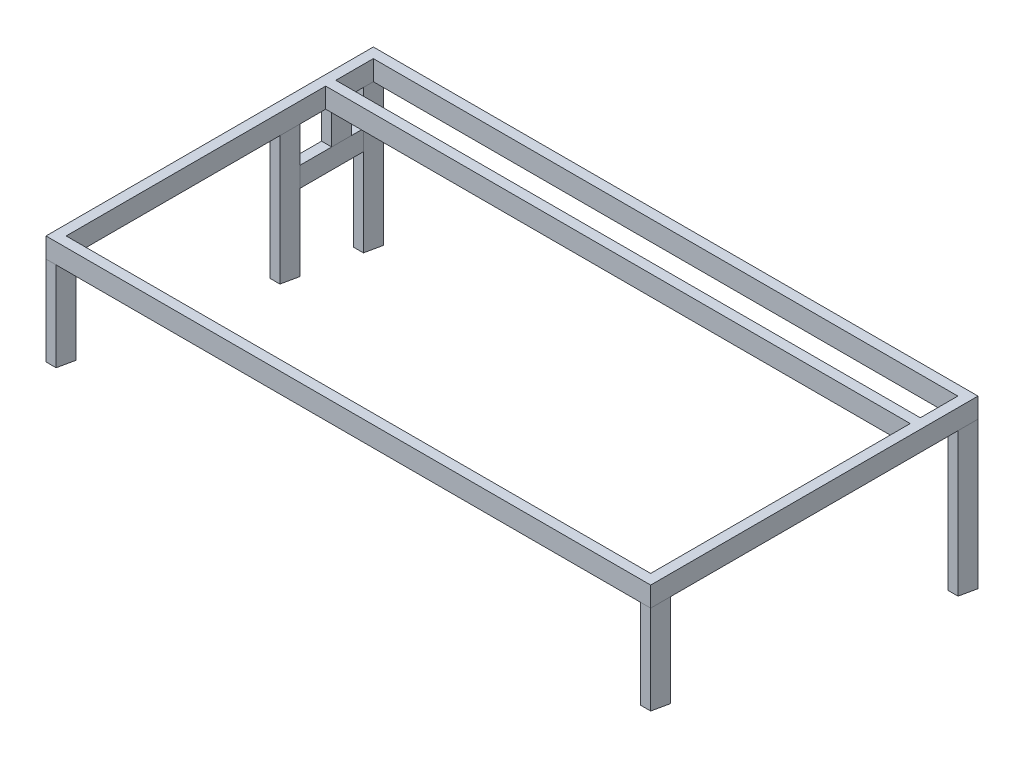
SolidWorks part; units mm, degrees
ref_plane "Front Plane" through (0, 0, 0) normal (0, 0, 1) x (1, 0, 0)
ref_plane "Top Plane" through (0, 0, 0) normal (0, 1, 0) x (1, 0, 0)
ref_plane "Right Plane" through (0, 0, 0) normal (1, 0, 0) x (0, 0, -1)
sketch "Sketch22" plane through (0, 0, 0) normal (0, 1, 0) x (1, 0, 0)
  line L0 (-736.6, 387.1) -> (736.6, 387.1)
  line L1 (-762, 412.5) -> (762, 412.5)
  line L2 (-762, 412.5) -> (-762, -412.5)
  line L3 (-762, -412.5) -> (762, -412.5)
  line L4 (762, 412.5) -> (762, -412.5)
  line L5 (-762, 412.5) -> (762, -412.5) construction
  line L6 (-762, -412.5) -> (762, 412.5) construction
  line L7 (736.6, 387.1) -> (736.6, -387.1)
  line L8 (-736.6, -387.1) -> (736.6, -387.1)
  line L9 (-736.6, 387.1) -> (-736.6, -387.1)
  point P0 (0, 0)
  dimension "D1" = 1524
  dimension "D2" = 825
  dimension "D3" = 25.4
extrude "Boss-Extrude3" add sketch "Sketch22" against normal blind 50.4
ref_plane "Plane1" through (0, -275, 0) normal (0, 1, 0) x (1, 0, 0)
ref_plane "Plane2" through (0, 0, 412.5) normal (0, 0, 1) x (1, 0, 0)
ref_axis "Axis1" through (-838.2, -275, 412.5) along (1, 0, 0)
ref_plane "LAUNCH PLANE" through (0, -337.2494, 59.4662) normal (0, 0.9848, -0.1736) x (1, 0, 0)
sketch "Sketch23" plane through (0, -50.4, 0) normal (0, -1, 0) x (1, 0, 0)
  line L0 (-736.6, -387.1) -> (-736.6, 387.1) construction
  line L1 (-762, 412.5) -> (-736.6, 412.5)
  line L2 (-762, 412.5) -> (-762, 362.1)
  line L3 (-762, 362.1) -> (-736.6, 362.1)
  line L4 (-736.6, 412.5) -> (-736.6, 362.1)
  line L5 (0, 0) -> (0, 277.5925) construction
  line L6 (736.6, 412.5) -> (736.6, 362.1)
  line L7 (762, 362.1) -> (736.6, 362.1)
  line L8 (762, 412.5) -> (762, 362.1)
  line L9 (762, 412.5) -> (736.6, 412.5)
  dimension "D1" = 50.4
extrude "Boss-Extrude4" add sketch "Sketch23" along normal up to surface (224.6 mm away) separate body up to plane "LAUNCH PLANE"
sketch "Sketch24" plane through (0, -50.4, 0) normal (0, -1, 0) x (1, 0, 0)
  line L0 (-736.6, -387.1) -> (-736.6, 387.1) construction
  line L1 (-762, -412.5) -> (-736.6, -412.5)
  line L2 (-762, -412.5) -> (-762, -362.1)
  line L3 (-762, -362.1) -> (-736.6, -362.1)
  line L4 (-736.6, -412.5) -> (-736.6, -362.1)
  line L5 (0, 0) -> (0, -131.3731) construction
  line L6 (736.6, -412.5) -> (736.6, -362.1)
  line L7 (762, -362.1) -> (736.6, -362.1)
  line L8 (762, -412.5) -> (762, -362.1)
  line L9 (762, -412.5) -> (736.6, -412.5)
  line L10 (-762, -412.5) -> (-762, 412.5) construction
  line L16 (-736.6, -202.1) -> (-762, -202.1)
  line L17 (-736.6, -202.1) -> (-736.6, -151.7)
  line L18 (-736.6, -151.7) -> (-762, -151.7)
  line L19 (-762, -202.1) -> (-762, -151.7)
  dimension "D1" = 50.4
  dimension "D2" = 160
  dimension "D3" = 50.4
extrude "Boss-Extrude5" add sketch "Sketch24" along normal up to surface (370.0698 mm away) separate body up to plane "LAUNCH PLANE"
sketch "Sketch26" plane through (0, 0, 0) normal (0, 1, 0) x (1, 0, 0)
  line L0 (-736.6, 387.1) -> (-736.6, -387.1) construction
  line L1 (-736.6, 292.5) -> (736.6, 292.5)
  line L2 (-736.6, 292.5) -> (-736.6, 267.1)
  line L3 (-736.6, 267.1) -> (736.6, 267.1)
  line L4 (736.6, 292.5) -> (736.6, 267.1)
  line L5 (736.6, -387.1) -> (736.6, 387.1) construction
  line L7 (736.6, 387.1) -> (-736.6, 387.1) construction
  dimension "D1" = 25.4
  dimension "D2" = 120
extrude "Boss-Extrude6" add sketch "Sketch26" against normal up to surface (50.4 mm away) up to face at (0, -50.4, 0)
sketch "Sketch25" plane through (762, 0, 0) normal (1, 0, 0) x (0, 0, -1)
  line L0 (362.1, -394.143) -> (412.5, -403.0299)
  line L2 (362.1, -411.5829) -> (362.1, -50.4) construction
  line L3 (412.5, -420.4698) -> (412.5, -50.4) construction
  line L4 (412.5, -403.0299) -> (412.5, -420.4698)
  line L5 (412.5, -420.4698) -> (-412.5, -420.4698)
  line L6 (-412.5, -420.4698) -> (-412.5, -257.5601)
  line L7 (-412.5, -275) -> (-412.5, -50.4) construction
  line L8 (-412.5, -257.5601) -> (-362.1, -266.447)
  line L9 (-362.1, -283.8869) -> (-362.1, -50.4) construction
  line L10 (-362.1, -266.447) -> (-362.1, -283.8869)
  line L11 (-362.1, -283.8869) -> (362.1, -394.143)
  line L12 (412.5, -50.4) -> (362.1, -50.4) construction
  dimension "D1" = 207.1601
  dimension "D2" = 216.047
sketch "Sketch27" plane through (0, 0, -202.1) normal (0, 0, -1) x (-1, 0, 0)
  line L0 (736.6, -420.4698) -> (736.6, -50.4) construction
  line L1 (736.6, -140.4) -> (762, -140.4)
  line L2 (736.6, -140.4) -> (736.6, -190.8)
  line L3 (736.6, -190.8) -> (762, -190.8)
  line L4 (762, -140.4) -> (762, -190.8)
  line L5 (762, -420.4698) -> (762, -50.4) construction
  line L6 (762, -50.4) -> (736.6, -50.4) construction
  dimension "D1" = 50.4
  dimension "D2" = 90
extrude "Boss-Extrude7" add sketch "Sketch27" along normal up to surface (160 mm away) separate body up to face at (-749.3, -230.9914, -362.1)
sketch "Sketch29" plane through (0, -50.4, 0) normal (0, -1, 0) x (1, 0, 0)
  line L0 (-736.6, -387.1) -> (-736.6, -292.5) construction
  line L1 (-736.6, -332.5) -> (-762, -332.5)
  line L2 (-736.6, -332.5) -> (-736.6, -282.1)
  line L3 (-736.6, -282.1) -> (-762, -282.1)
  line L4 (-762, -332.5) -> (-762, -282.1)
  line L5 (-762, -362.1) -> (-762, -202.1) construction
  line L6 (-736.6, -202.1) -> (-762, -202.1) construction
  dimension "D1" = 50.4
  dimension "D2" = 80
extrude "Boss-Extrude8" add sketch "Sketch29" along normal up to surface (90 mm away) separate body up to face at (-749.3, -140.4, -282.1)
